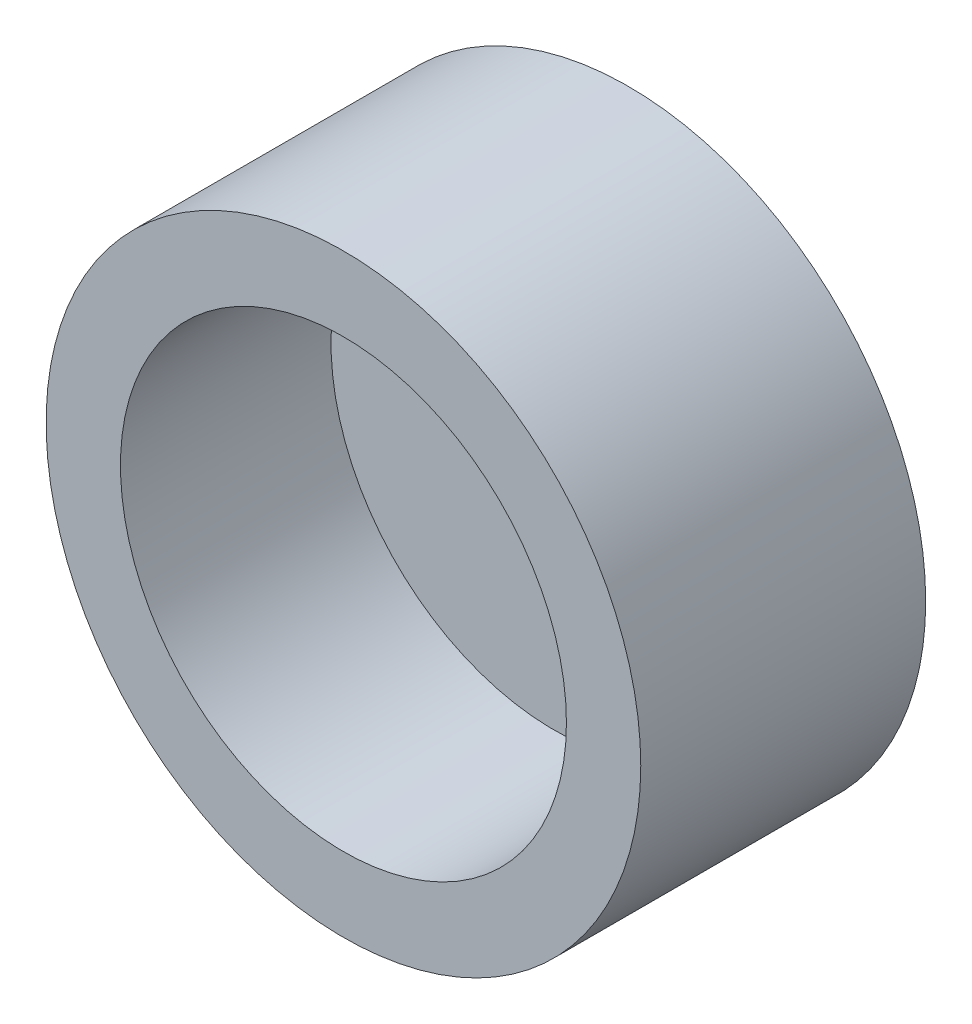
SolidWorks part; units mm, degrees
ref_plane "Front Plane" through (0, 0, 0) normal (0, 0, 1) x (1, 0, 0)
ref_plane "Top Plane" through (0, 0, 0) normal (0, 1, 0) x (1, 0, 0)
ref_plane "Right Plane" through (0, 0, 0) normal (1, 0, 0) x (0, 0, -1)
sketch "Sketch1" plane through (0, 0, 0) normal (0, 0, 1) x (1, 0, 0)
  circle A0 centre (0, 0) radius 9
  circle A1 centre (0, 0) radius 12
  dimension "D1" = 3
  dimension "D2" = 18
extrude "Boss-Extrude1" add sketch "Sketch1" along normal blind 8.5
extrude "Boss-Extrude2" add sketch "Sketch1<2>" against normal blind 3 contours A1
sketch "Sketch1<2>" plane through (0, 0, 0) normal (0, 0, 1) x (1, 0, 0) same geometry as "Sketch1"
sketch "Sketch2" plane through (0, 0, -3) normal (0, 0, -1) x (-1, 0, 0)
  circle A0 centre (0, 0) radius 5
  dimension "D1" = 10
extrude "Cut-Extrude1" cut sketch "Sketch2" against normal blind 2
